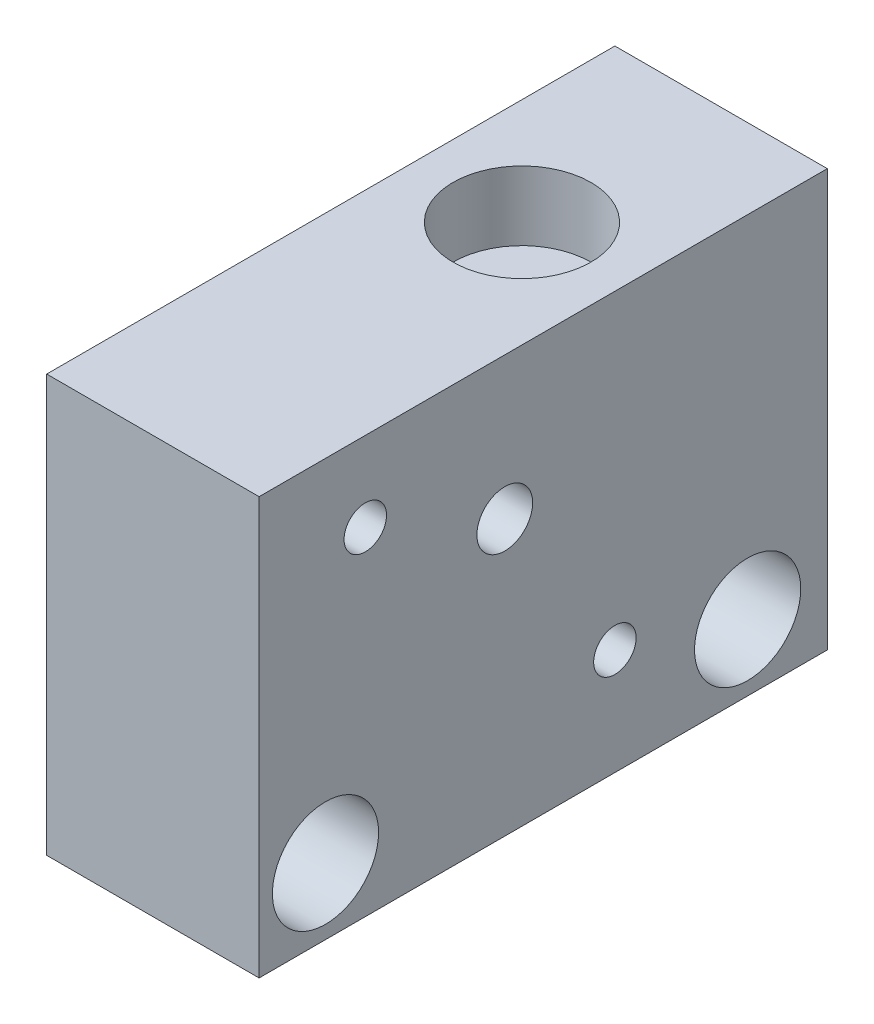
SolidWorks part; units mm, degrees
ref_plane "前视基准面" through (0, 0, 0) normal (0, 0, 1) x (1, 0, 0)
ref_plane "上视基准面" through (0, 0, 0) normal (0, 1, 0) x (1, 0, 0)
ref_plane "右视基准面" through (0, 0, 0) normal (1, 0, 0) x (0, 0, -1)
other "Configuration Table"
sketch "草图1" plane through (0, 0, 0) normal (0, 1, 0) x (1, 0, 0)
  line L33 (-4, -13.9) -> (4, -13.9)
  line L34 (-4, -13.9) -> (-4, 7.5)
  line L35 (-4, 7.5) -> (4, 7.5)
  line L36 (4, -13.9) -> (4, 7.5)
  line L37 (-4, -13.9) -> (4, 7.5) construction
  line L38 (-4, 7.5) -> (4, -13.9) construction
  circle A0 centre (0, 0) radius 2.6
  point P0 (-90.6464, 22.0667)
  point P9 (0, -3.2)
  dimension "D1" = 5.2
  dimension "D2" = 7.5
  dimension "D3" = 21.4
  dimension "D6" = 8
extrude "凸台-拉伸1" add sketch "草图1" along normal blind 15.7 contours L33 | L34 | L33 L36 L35 L34 region at (0, 0, 3.6532)
extrude "切除-拉伸1" cut sketch "草图1<18>" against normal blind 2.6 from surface contours A0 starting at face at (0, 15.7, 3.2)
sketch "草图1<18>" plane through (0, 0, 0) normal (0, 1, 0) x (1, 0, 0) same geometry as "草图1"
sketch "草图2" plane through (-4, 0, 0) normal (-1, 0, 0) x (0, 0, 1)
  circle A0 centre (4.6468, 10.3503) radius 1.05
  point P2 (4.6468, 10.3503)
  point P4 (0, 0)
  dimension "D1" = 2.1
extrude "切除-拉伸2" cut sketch "草图2" against normal through all contours A0
sketch "草图3" plane through (4, 0, 0) normal (1, 0, 0) x (0, 0, -1)
  circle A0 centre (4.5, 2.5) radius 2
  circle A1 centre (4.5, 2.5) radius 1.5
  circle A2 centre (-11.4, 2.5) radius 2
  circle A3 centre (-11.4, 2.5) radius 1.5
  point P6 (-9.7845, -6.1035)
  point P7 (-11.4, 2.5)
  point P9 (4.5, 2.5)
  point P11 (0, 0)
  point P12 (0, 0)
  dimension "D1" = 3
  dimension "D2" = 4
extrude "切除-拉伸4" cut sketch "草图3" against normal offset from surface (6 mm away) 2 contours A0 | A2 up to face at (-4, 10.3503, 5.6968)
extrude "切除-拉伸5" cut sketch "草图3<4>" against normal through all contours A3 | A1
sketch "草图3<4>" plane through (4, 0, 0) normal (1, 0, 0) x (0, 0, -1) same geometry as "草图3"
sketch "草图4" plane through (4, 0, 0) normal (1, 0, 0) x (0, 0, -1)
  line L0 (-13.9, 0) -> (7.5, 0) construction
  line L1 (-13.9, 15.7) -> (-13.9, 0) construction
  line L2 (-13.9, 15.7) -> (7.5, 15.7) construction
  line L3 (7.5, 15.7) -> (7.5, 0) construction
  circle A1 centre (-0.5, 4) radius 0.8
  circle A3 centre (-9.9, 12.7) radius 0.8
  point P10 (0, 0)
  dimension "D1" = 1.6
  dimension "D2" = 4
  dimension "D3" = 4
  dimension "D4" = 3
  dimension "D5" = 8
extrude "切除-拉伸6" cut sketch "草图4" against normal blind 4 contours A3 | A1
